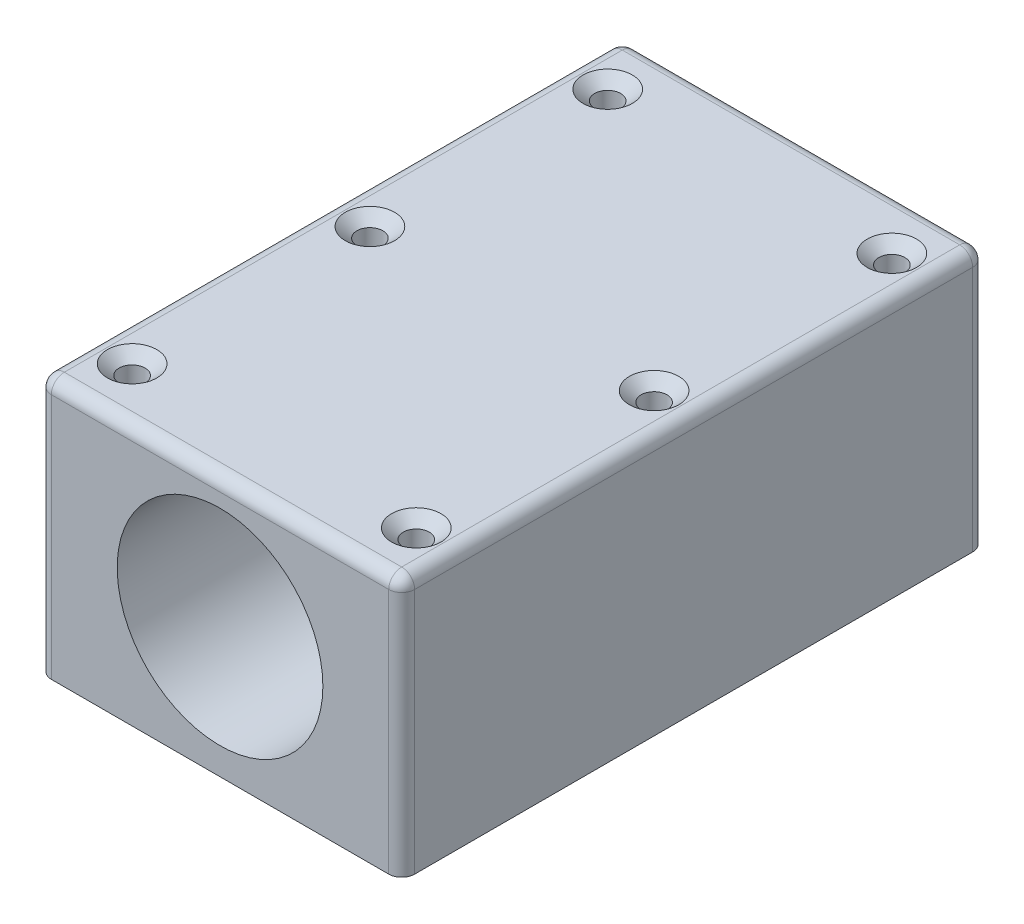
SolidWorks part; units mm, degrees
ref_plane "Front Plane" through (0, 0, 0) normal (0, 0, 1) x (1, 0, 0)
ref_plane "Top Plane" through (0, 0, 0) normal (0, 1, 0) x (1, 0, 0)
ref_plane "Right Plane" through (0, 0, 0) normal (1, 0, 0) x (0, 0, -1)
sketch "Sketch1" plane through (0, 0, 0) normal (0, 0, 1) x (1, 0, 0)
  line L0 (0, 25.4) -> (71.12, 25.4) construction
  line L1 (0, 0) -> (71.12, 0)
  line L2 (0, 0) -> (0, 50.8)
  line L3 (0, 50.8) -> (71.12, 50.8)
  line L4 (71.12, 0) -> (71.12, 50.8)
  line L5 (15.4305, 25.4) -> (15.4305, 50.8) construction
  line L6 (55.6895, 25.4) -> (55.6895, 50.8) construction
  circle A0 centre (35.56, 25.4) radius 20.1295
  dimension "D3" = 40.259
  dimension "D1" = 50.8
  dimension "D2" = 71.12
extrude "Boss-Extrude1" add sketch "Sketch1" along normal blind 114.3
sketch "Sketch2" plane through (0, 50.8, 0) normal (0, 1, 0) x (1, 0, 0)
  line L0 (35.56, 0) -> (35.56, -114.3) construction
  line L1 (71.12, 0) -> (0, 0) construction
  line L2 (71.12, -114.3) -> (0, -114.3) construction
  line L3 (15.494, -114.3) -> (15.494, 0) construction
  line L4 (15.4305, -114.3) -> (55.6895, -114.3) construction
  line L5 (15.494, 0) -> (0, 0) construction
  line L6 (7.747, 0) -> (7.747, -114.3) construction
  line L7 (0, -57.15) -> (71.12, -57.15) construction
  line L8 (0, -114.3) -> (0, 0) construction
  line L9 (71.12, -114.3) -> (71.12, 0) construction
  circle A0 centre (7.747, -10.6045) radius 2.54
  circle A1 centre (7.747, -10.6045) radius 4.826
  circle A2 centre (7.747, -103.6955) radius 2.54
  circle A3 centre (7.747, -103.6955) radius 4.826
  circle A4 centre (7.747, -57.15) radius 2.54
  circle A5 centre (7.747, -57.15) radius 4.826
  circle A6 centre (63.373, -103.6955) radius 2.54
  circle A7 centre (63.373, -103.6955) radius 4.826
  circle A8 centre (63.373, -57.15) radius 4.826
  circle A9 centre (63.373, -57.15) radius 2.54
  circle A10 centre (63.373, -10.6045) radius 2.54
  circle A11 centre (63.373, -10.6045) radius 4.826
  dimension "D2" = 5.08
  dimension "D4" = 9.652
  dimension "D5" = 5.08
  dimension "D6" = 9.652
  dimension "D1" = 20.066
  dimension "D3" = 10.6045
extrude "Cut-Extrude1" cut sketch "Sketch2" against normal up to surface (50.8 mm away) contours A2 | A4 | A0 | A10 | A9 | A6 region at (7.747, 50.8, 10.6045) region at (7.747, 50.8, 103.6955) region at (7.747, 50.8, 57.15) region at (63.373, 50.8, 103.6955) region at (63.373, 50.8, 57.15) region at (63.373, 50.8, 10.6045) up to face at (35.56, 0, 57.15)
extrude "Cut-Extrude2" cut sketch "Sketch2<3>" against normal blind 3.2258 draft 49 contours A3 A2 | A2 | A4 | A5 A4 | A0 | A1 A0 | A10 | A11 A10 | A9 | A8 A9 | A6 | A7 A6 region at (7.747, 50.8, 10.6045) region at (3.0575, 50.8, 10.6045) region at (7.747, 50.8, 103.6955) region at (3.0575, 50.8, 103.6955) region at (7.747, 50.8, 57.15) region at (3.0575, 50.8, 57.15) region at (63.373, 50.8, 103.6955) region at (58.6835, 50.8, 103.6955) region at (58.6835, 50.8, 57.15) region at (63.373, 50.8, 57.15) region at (63.373, 50.8, 10.6045) region at (58.6835, 50.8, 10.6045)
sketch "Sketch2<3>" plane through (0, 50.8, 0) normal (0, 1, 0) x (1, 0, 0) same geometry as "Sketch2"
fillet "Fillet1" radius 2.54 8 edges at (0, 25.4, 0) (71.12, 25.4, 0) (0, 25.4, 114.3) (71.12, 25.4, 114.3) (35.56, 50.8, 0) (71.12, 50.8, 57.15) (0, 50.8, 57.15) (35.56, 50.8, 114.3)
